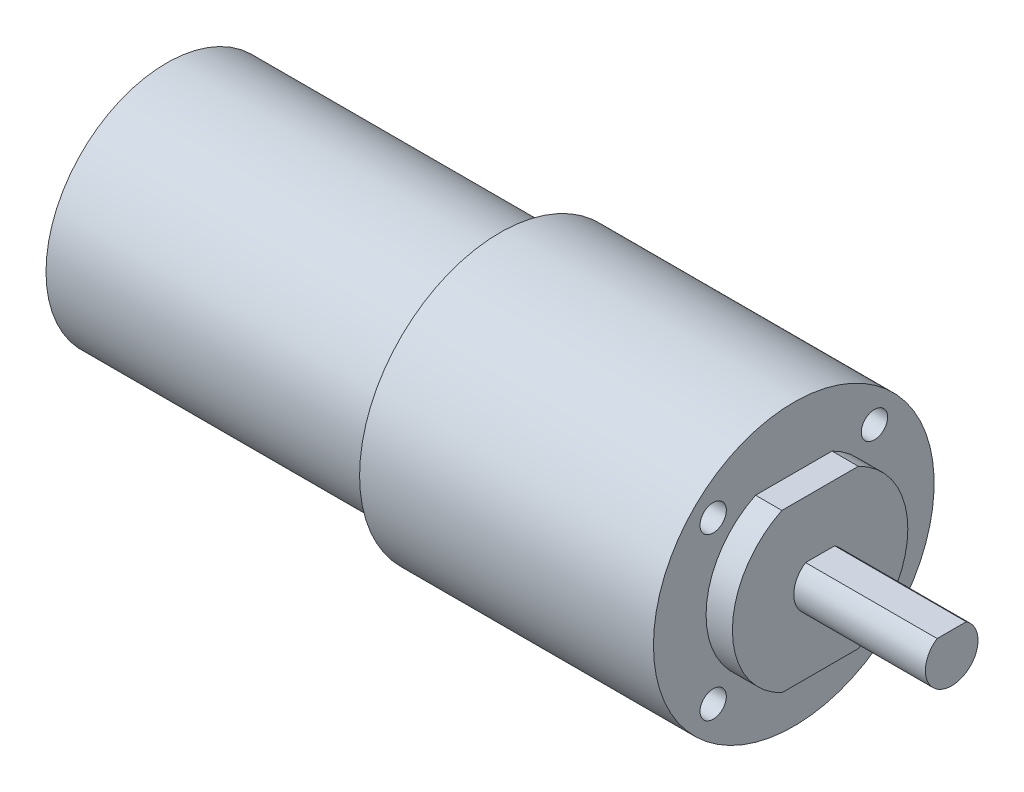
SolidWorks part; units mm, degrees
ref_plane "Front Plane" through (0, 0, 0) normal (0, 0, 1) x (1, 0, 0)
ref_plane "Top Plane" through (0, 0, 0) normal (0, 1, 0) x (1, 0, 0)
ref_plane "Right Plane" through (0, 0, 0) normal (1, 0, 0) x (0, 0, -1)
ref_axis "Axe1" through (-42.475, 0, 0) along (1, 0, 0)
sketch "Esquisse1" plane through (0, 0, 0) normal (0, 0, 1) x (1, 0, 0)
  line L0 (-38, 13.75) -> (0, 13.75)
  line L1 (0, 13.75) -> (0, 16)
  line L2 (0, 16) -> (33.5, 16)
  line L3 (33.5, 16) -> (33.5, 10)
  line L4 (33.5, 10) -> (36.5, 10)
  line L5 (36.5, 10) -> (36.5, 3)
  line L6 (36.5, 3) -> (51.5, 3)
  line L7 (51.5, 3) -> (51.5, 0)
  line L8 (51.5, 0) -> (-38, 0)
  line L9 (-38, 0) -> (-38, 13.75)
  point P5 (37.2837, 0)
  dimension "D1" = 3
  dimension "D2" = 10
  dimension "D3" = 16
  dimension "D4" = 15
  dimension "D5" = 3
  dimension "D6" = 33.5
  dimension "D7" = 38
  dimension "D8" = 13.75
revolve "Révolution1" add sketch "Esquisse1" angle 360 about axis through (-42.475, 0, 0) along (1, 0, 0)
sketch "Esquisse2" plane through (36.5, 0, 0) normal (1, 0, 0) x (0, 0, -1)
  line L0 (-4.3589, 9) -> (4.3589, 9)
  line L1 (-4.3589, -9) -> (4.3589, -9)
  circle A0 centre (0, 0) radius 10 construction
  circle A1 centre (0, 0) radius 10 construction
  arc A2 (-4.3589, 9) -> (4.3589, 9) centre (0, 0) cw
  arc A3 (4.3589, -9) -> (-4.3589, -9) centre (0, 0) cw
  dimension "D1" = 9
  dimension "D2" = 9
extrude "MeplatFixing" cut sketch "Esquisse2" against normal up to surface (3 mm away) up to face at (33.5, 0, 16)
sketch "Esquisse3" plane through (51.5, 0, 0) normal (1, 0, 0) x (0, 0, -1)
  line L0 (-1.6583, 2.5) -> (1.6583, 2.5)
  circle A0 centre (0, 0) radius 3 construction
  arc A1 (-1.6583, 2.5) -> (1.6583, 2.5) centre (0, 0) cw
  dimension "D1" = 2.5
extrude "MeplatRotor" cut sketch "Esquisse3" against normal up to surface (15 mm away) up to face at (36.5, 0, 0)
sketch "Esquisse4" plane through (33.5, 0, 0) normal (1, 0, 0) x (0, 0, -1)
  line L0 (0, 0) -> (22.8047, 0) construction
  line L1 (0, 0) -> (9.1924, 9.1924) construction
  circle A0 centre (9.1924, 9.1924) radius 1.5
  dimension "D1" = 3
  dimension "D2" = 13
  dimension "D3" = 45
extrude "FixingHole" cut sketch "Esquisse4" against normal blind 5
pattern_circular "FixingHoleCircularRepetition" count 4 over 360 about axis through (-42.475, 0, 0) along (1, 0, 0) of "FixingHole"
